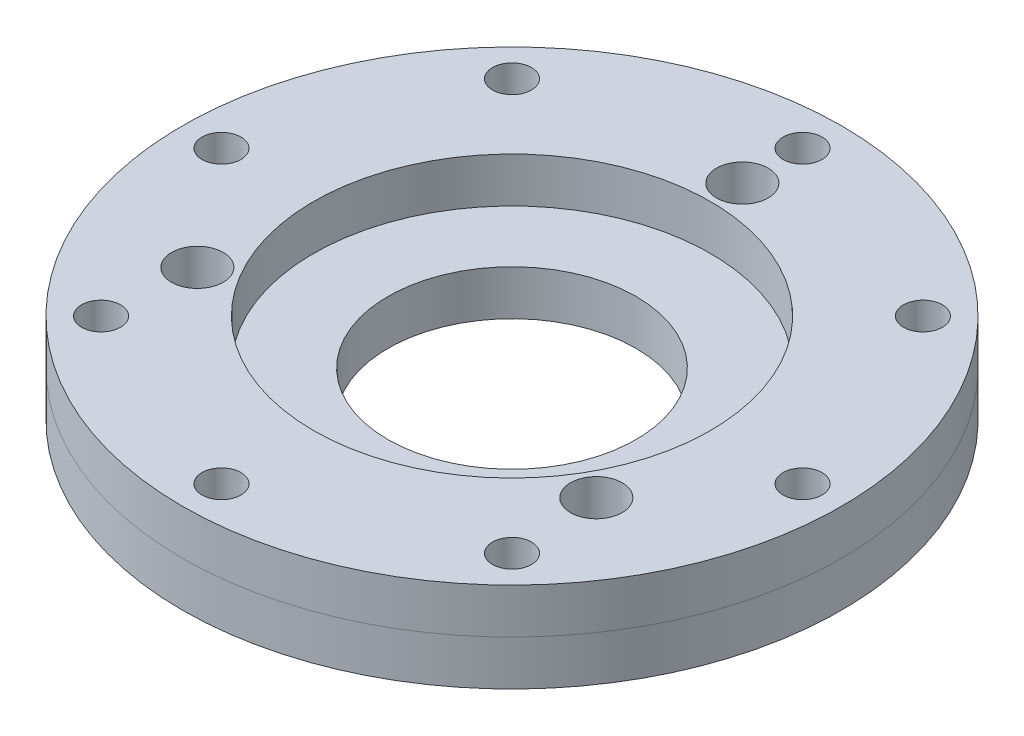
SolidWorks part; units mm, degrees
ref_plane "Front Plane" through (0, 0, 0) normal (0, 0, 1) x (1, 0, 0)
ref_plane "Top Plane" through (0, 0, 0) normal (0, 1, 0) x (1, 0, 0)
ref_plane "Right Plane" through (0, 0, 0) normal (1, 0, 0) x (0, 0, -1)
sketch "Sketch1" plane through (0, 0, 0) normal (0, 1, 0) x (1, 0, 0)
  circle A0 centre (0, 0) radius 46.5
  circle A1 centre (0, 0) radius 32.5 construction
  circle A2 centre (0, 32.5) radius 2.25
  circle A3 centre (28.1458, -16.25) radius 2.25
  circle A4 centre (-28.1458, -16.25) radius 2.25
  circle A5 centre (0, 0) radius 17.5
  point P13 (0, 0)
  dimension "D1" = 93
  dimension "D2" = 65
  dimension "D3" = 4.5
  dimension "D5" = 35
  dimension "D4" = 3
extrude "Boss-Extrude1" add sketch "Sketch1" along normal blind 12.7
sketch "Sketch2" plane through (0, 12.7, 0) normal (0, 1, 0) x (1, 0, 0)
  circle A0 centre (0, 0) radius 28
  dimension "D1" = 56
extrude "Cut-Extrude1" cut sketch "Sketch2" against normal blind 6.35
sketch "Sketch3" plane through (0, 12.7, 0) normal (0, 1, 0) x (1, 0, 0)
  line L0 (0, 41) -> (0, 0) construction
  circle A0 centre (0, 0) radius 41 construction
  circle A1 centre (0, 41) radius 2.75
  circle A2 centre (28.9914, 28.9914) radius 2.75
  circle A3 centre (41, 0) radius 2.75
  circle A4 centre (28.9914, -28.9914) radius 2.75
  circle A5 centre (0, -41) radius 2.75
  circle A6 centre (-28.9914, -28.9914) radius 2.75
  circle A7 centre (-41, 0) radius 2.75
  circle A8 centre (-28.9914, 28.9914) radius 2.75
  point P21 (0, 0)
  dimension "D1" = 82
  dimension "D2" = 5.5
  dimension "D3" = 8
extrude "Cut-Extrude2" cut sketch "Sketch3" against normal blind 6.35
sketch "Sketch4" plane through (0, 12.7, 0) normal (0, 1, 0) x (1, 0, 0)
  circle A0 centre (0, 32.5) radius 3.65
  circle A1 centre (28.1458, -16.25) radius 3.65
  circle A2 centre (-28.1458, -16.25) radius 3.65
  circle A3 centre (-28.1458, -16.25) radius 2.25 construction
  point P9 (0, 0)
  point P64 (0, 0)
  dimension "D1" = 3
  dimension "8" = 7.3
extrude "Cut-Extrude3" cut sketch "Sketch4" against normal blind 6.35
split "Split1" bodies to split 105 resulting bodies 108 109 split by face at (0, 6.35, 17.5)
sketch "Sketch5" plane through (0, 12.7, 0) normal (0, 1, 0) x (1, 0, 0)
  line L0 (0, 0) -> (0, 41) construction
  circle A0 centre (-28.9914, 28.9914) radius 2.75 construction
  circle A1 centre (0, 0) radius 41 construction
  circle A2 centre (-28.9914, 28.9914) radius 2.75 construction
  circle A3 centre (0, 0) radius 41 construction
  circle A4 centre (0, 41) radius 2.75 construction
  circle A5 centre (0, 41) radius 2.75 construction
  circle A6 centre (0, 41) radius 2.1
  circle A7 centre (28.9914, 28.9914) radius 2.1
  circle A8 centre (41, 0) radius 2.1
  circle A9 centre (28.9914, -28.9914) radius 2.1
  circle A10 centre (0, -41) radius 2.1
  circle A11 centre (-28.9914, -28.9914) radius 2.1
  circle A12 centre (-41, 0) radius 2.1
  circle A13 centre (-28.9914, 28.9914) radius 2.1
  point P0 (-28.9914, 28.9914)
  point P30 (0, 0)
  dimension "D1" = 4.2
  dimension "D3" = 41
  dimension "D2" = 8
extrude "Cut-Extrude4" cut sketch "Sketch5" against normal through all
